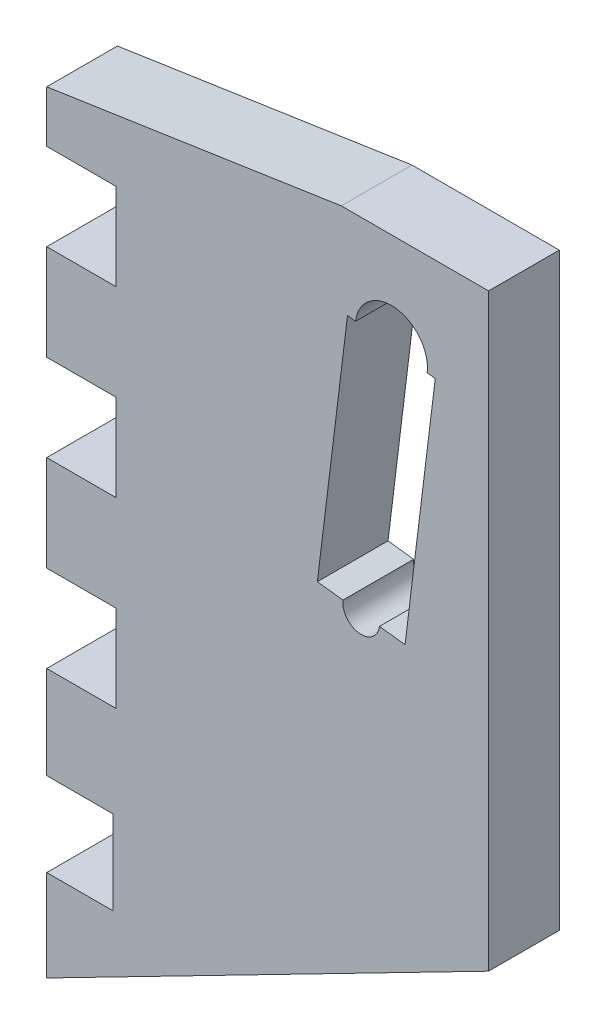
SolidWorks part; units mm, degrees
material "Thornel VCB-20 Carbon Cloth"
ref_plane "Front Plane" through (0, 0, 0) normal (0, 0, 1) x (1, 0, 0)
ref_plane "Top Plane" through (0, 0, 0) normal (0, 1, 0) x (1, 0, 0)
ref_plane "Right Plane" through (0, 0, 0) normal (1, 0, 0) x (0, 0, -1)
sketch "Sketch1" plane through (0, 0, 0) normal (0, 0, 1) x (1, 0, 0)
  line L0 (0, 0) -> (-38.1, 0)
  line L1 (0, 0) -> (0, -50.8)
  line L2 (-38.1, 0) -> (-38.1, -8.255)
  line L3 (-38.1, -8.255) -> (-32.131, -8.255)
  line L4 (-32.131, -8.255) -> (-32.131, -15.748)
  line L5 (-32.131, -15.748) -> (-38.1, -15.748)
  line L6 (-38.1, -47.244) -> (-38.1, -70.358)
  line L7 (-38.1, -15.748) -> (-38.1, -24.003)
  line L8 (-38.1, -24.003) -> (-32.131, -24.003)
  line L9 (-32.131, -24.003) -> (-32.131, -31.496)
  line L10 (-32.131, -31.496) -> (-38.1, -31.496)
  line L11 (-38.1, -31.496) -> (-38.1, -39.751)
  line L12 (-38.1, -39.751) -> (-32.131, -39.751)
  line L13 (-32.131, -39.751) -> (-32.131, -47.244)
  line L14 (-32.131, -47.244) -> (-38.1, -47.244)
  line L15 (-38.1, -70.358) -> (0, -50.8)
  circle A0 centre (-8.382, -8.382) radius 3.1115
  dimension "D9" = 6.223
  dimension "D1" = 38.1
  dimension "D2" = 50.8
  dimension "D3" = 8.255
  dimension "D4" = 7.493
  dimension "D6" = 5.969
  dimension "D8" = 70.358
  dimension "D12" = 8.382
  dimension "D13" = 8.382
  dimension "D7" = 3
extrude "Boss-Extrude1" add sketch "Sketch1" along normal blind 6.096 contours L6 L15 L1 L0 L2 L3 L4 L5 L7 L8 L9 L10 L11 L12 L13 L14 A0 region at (-19.2995, -31.0427, 0)
sketch "Sketch2" plane through (0, 0, 0) normal (0, 0, -1) x (-1, 0, 0)
  line L5 (38.1, 0) -> (12.7, 0)
  line L6 (0, 0) -> (38.1, 0) construction
  line L7 (12.7, 0) -> (38.1, -3.81)
  line L8 (38.1, 0) -> (38.1, -8.255) construction
  line L9 (38.1, -3.81) -> (38.1, 0)
  dimension "D1" = 25.4
  dimension "D2" = 3.81
extrude "Cut-Extrude1" cut sketch "Sketch2" against normal blind 8.636
sketch "Sketch4" plane through (0, 0, 6.096) normal (0, 0, 1) x (1, 0, 0)
  line L0 (-38.1, -47.244) -> (-38.1, -55.245)
  line L1 (-38.1, -47.244) -> (-38.1, -70.358) construction
  line L2 (-38.1, -55.245) -> (-32.385, -55.245)
  line L3 (-32.385, -55.245) -> (-32.385, -62.484)
  line L4 (-32.385, -62.484) -> (-38.1, -62.484)
  line L5 (-38.1, -62.484) -> (-38.1, -55.245)
  line M18 (-38.1, -47.244) -> (-38.1, -70.358)
  dimension "D1" = 7.239
  dimension "D2" = 5.715
  dimension "D3" = 5.715
  dimension "D4" = 8.001
extrude "Cut-Extrude2" cut sketch "Sketch4" against normal through all contours L4 L3 L2 M18 region at (-35.2425, -58.8645, 6.096)
sketch "Sketch5" plane through (0, 0, 0) normal (0, 0, -1) x (-1, 0, 0)
  line L0 (8.382, -8.382) -> (10.9822, -29.559) construction
  line L1 (8.382, -8.382) -> (8.382, -39.2411) construction
  circle A0 centre (8.382, -8.382) radius 3.1115 construction
  circle A1 centre (10.9822, -29.559) radius 1.5875
  dimension "D3" = 3.175
  dimension "D1" = 21.336
  dimension "D2" = 7
extrude "Cut-Extrude4" cut sketch "Sketch5" against normal up to surface (6.096 mm away) up to face at (-5.2705, -8.382, 6.096)
sketch "Sketch6" plane through (0, 0, 6.096) normal (0, 0, 1) x (1, 0, 0)
  line L0 (-5.2307, -8.7689) -> (-4.6004, -8.8463)
  line L1 (-11.5333, -7.9951) -> (-12.1636, -7.9177)
  line L6 (-14.7638, -29.0946) -> (-12.6209, -29.3578)
  line L7 (-4.6004, -8.8463) -> (-7.2006, -30.0233)
  line L8 (-12.1636, -7.9177) -> (-14.7638, -29.0946)
  line L10 (-9.3435, -29.7602) -> (-7.2006, -30.0233)
  line L11 (-12.6209, -29.3578) -> (-9.3435, -29.7602)
  line L12 (-11.5333, -7.9951) -> (-5.2307, -8.7689)
  dimension "D5" = 21.336
  dimension "D2" = 0.635
  dimension "D3" = 0.635
extrude "Cut-Extrude5" cut sketch "Sketch6" against normal up to surface (6.096 mm away) up to face at (-12.5697, -29.559, 0)
